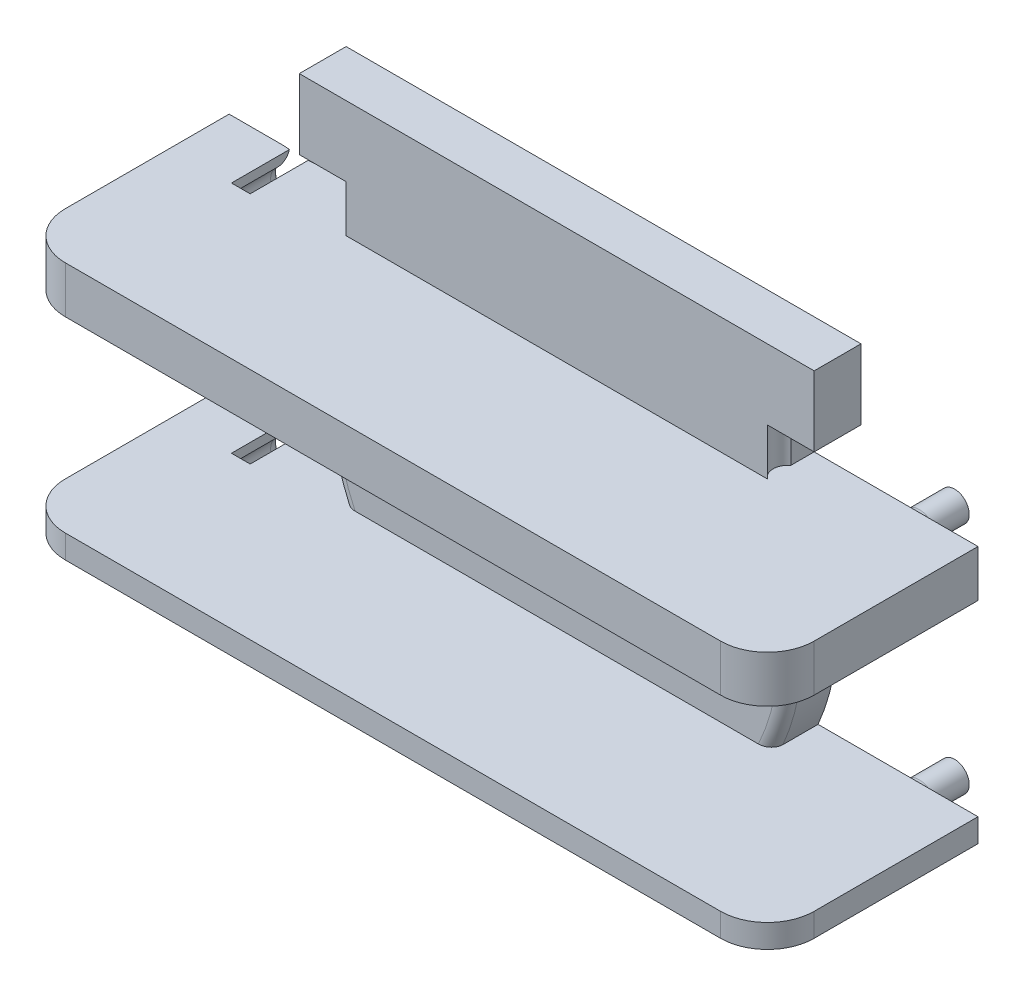
SolidWorks part; units mm, degrees
material "UNOBTANIUM"
ref_plane "Top Plane" through (0, 0, 0) normal (0, 0, 1) x (1, 0, 0)
ref_plane "Right Plane" through (0, 0, 0) normal (0, 1, 0) x (1, 0, 0)
ref_plane "Front Plane" through (0, 0, 0) normal (1, 0, 0) x (0, 0, -1)
ref_axis "x-axis" through (-17.6, 0, 0) along (1, 0, 0)
ref_axis "y-axis" through (0, -9.7375, 0) along (0, 1, 0)
ref_axis "z-axis" through (0, 0, 8.775) along (0, 0, -1)
sketch "Sketch1" plane through (0, 0, 0) normal (0, 0, 1) x (1, 0, 0)
  line L0 (-11, 6) -> (-11, 11)
  line L1 (-11, -6) -> (11, -6)
  line L2 (-11, -6) -> (-11, 6)
  line L3 (-11, 6) -> (11, 6) construction
  line L4 (11, -6) -> (11, 6)
  line L5 (-11, -6) -> (11, 6) construction
  line L6 (-11, 6) -> (11, -6) construction
  line L7 (-11, 11) -> (11, 11)
  line L8 (11, 11) -> (11, 6)
  circle A0 centre (0, 0) radius 9.25 construction
  point P0 (0, 0)
  dimension "D1" = 18.5
  dimension "D2" = 22
  dimension "D3" = 12
  dimension "D4" = 5
extrude "Boss-Extrude1" add sketch "Sketch1" along normal blind 2
sketch "Sketch2" plane through (0, 0, 2) normal (0, 0, -1) x (-1, 0, 0)
  circle A0 centre (0, 0) radius 1.575
  dimension "D1" = 3.15
extrude "Boss-Extrude2" add sketch "Sketch2" along normal blind 4 separate body
sketch "Sketch3" plane through (0, 0, 0) normal (0, 0, -1) x (-1, 0, 0)
  line L0 (11, -6) -> (-11, 6) construction
  circle A0 centre (0, 0) radius 1.8
  dimension "D1" = 3.6
extrude "Boss-Extrude3" add sketch "Sketch3" along normal blind 0.75
sketch "Sketch4" plane through (0, 0, 0) normal (0, 0, -1) x (-1, 0, 0)
  line L0 (11, -6) -> (-11, -6) construction
  line L1 (11, 11) -> (9, 11)
  line L2 (11, 11) -> (11, -6)
  line L3 (11, -6) -> (9, -6)
  line L4 (9, 11) -> (9, -6)
  line L5 (0, -6) -> (0, 11) construction
  line L7 (-9, 11) -> (-9, -6)
  line L8 (-11, -6) -> (-9, -6)
  line L9 (-11, 11) -> (-11, -6)
  line L10 (-11, 11) -> (-9, 11)
  line L11 (11, 11) -> (-11, 11) construction
  dimension "D1" = 2
extrude "Boss-Extrude4" add sketch "Sketch4" along normal blind 0.001
sketch "Sketch5" plane through (0, 0, 0) normal (0, 0, -1) x (-1, 0, 0)
  line L0 (-9, -6) -> (-9, 11) construction
  line L1 (9, 11) -> (-9, 11)
  line L2 (9, 11) -> (9, 9)
  line L3 (9, 9) -> (-9, 9)
  line L4 (-9, 11) -> (-9, 9)
  dimension "D1" = 2
extrude "Boss-Extrude5" add sketch "Sketch5" along normal up to surface (0.001 mm away) up to face at (-10, 2.5, -0.001)
sketch "Sketch6" plane through (11, 0, 0) normal (1, 0, 0) x (0, 0, -1)
  line L0 (-2, -6) -> (-2, 11) construction
  line L1 (0.001, -6) -> (-2, -6)
  line L2 (0.001, -6) -> (0.001, -4)
  line L3 (0.001, -4) -> (-2, -4)
  line L4 (-2, -6) -> (-2, -4)
  line L6 (0.001, 11) -> (0.001, -6) construction
  line L7 (-2, 6) -> (0.001, 6)
  line L8 (-2, 6) -> (-2, 4)
  line L9 (-2, 4) -> (0.001, 4)
  line L10 (0.001, 6) -> (0.001, 4)
  dimension "D1" = 2
extrude "Boss-Extrude6" add sketch "Sketch6" along normal blind 5
mirror "Mirror1" about plane through (0, 0, 0) normal (1, 0, 0) of "Boss-Extrude6"
sketch "Sketch7" plane through (0, 0, -0.001) normal (0, 0, -1) x (-1, 0, 0)
  line L0 (-9, -6) -> (-9, 9) construction
  line L1 (-9, 0) -> (-9, 9)
  line L2 (-9, 9) -> (0, 9)
  line L3 (-9, 0) -> (-9, -6)
  line L4 (-9, -6) -> (-6.7082, -6)
  line L5 (11, -6) -> (-11, -6) construction
  arc A0 (0, 9) -> (-6.7082, -6) centre (0, 0) ccw
  line M18 (-9, -6) -> (-9, 9)
  line M19 (-9, 9) -> (9, 9)
extrude "Boss-Extrude7" add sketch "Sketch7" against normal up to surface (0.001 mm away) contours A0 L4 M18 | A0 M19 M18 region at (8.3306, -4.5409, -0.001) region at (6.9897, 6.9897, -0.001) up to face at (1.8, 0, 0)
sketch "Sketch8" plane through (0, 0, -0.001) normal (0, 0, -1) x (-1, 0, 0)
  line L0 (-11, 4) -> (-9.1652, 4)
  line L1 (-11, 4) -> (-11, -4)
  line L2 (-11, -4) -> (-9.1652, -4)
  arc A1 (-9.1652, 4) -> (-9.1652, -4) centre (0, 0) ccw
  dimension "D1" = 10
extrude "Cut-Extrude1" cut sketch "Sketch8" against normal through all
sketch "Sketch9" plane through (0, 0, -0.001) normal (0, 0, -1) x (-1, 0, 0)
  line L0 (-16, -4) -> (-9.1652, -4) construction
  line L1 (-8.0623, 4) -> (-11, 4)
  line L2 (-8.0623, 4) -> (-8.0623, -4)
  line L3 (-8.0623, -4) -> (-11, -4)
  line L4 (-11, 4) -> (-11, -4)
  line L5 (-11, -6) -> (-11, 6) construction
  arc A0 (0, 9) -> (-6.7082, -6) centre (0, 0) ccw construction
  arc A1 (0, 9) -> (-6.7082, -6) centre (0, 0) ccw construction
extrude "Cut-Extrude2" cut sketch "Sketch9" against normal up to surface (0.001 mm away) up to face at (1.8, 0, 0)
mirror "Mirror2" about plane through (0, 0, 0) normal (1, 0, 0) of "Cut-Extrude2", "Boss-Extrude7", "Cut-Extrude1"
sketch "Sketch21" plane through (0, 0, -0.001) normal (0, 0, -1) x (-1, 0, 0)
  circle A0 centre (0, 0) radius 9.75
  circle A1 centre (0, 0) radius 9 construction
  circle A2 centre (0, 0) radius 1.8 construction
  circle A3 centre (0, 0) radius 1.8
  dimension "D1" = 0.75
extrude "Cut-Extrude11" cut sketch "Sketch21" against normal up to surface (0.001 mm away) up to face at (0, -0.7091, 0)
sketch "Sketch10" plane through (0, 0, 2) normal (0, 0, 1) x (1, 0, 0)
  line L0 (-16, -4) -> (-16, -6) construction
  line L1 (16, -6) -> (-16, -6)
  line L2 (16, -6) -> (16, -4)
  line L3 (16, -4) -> (-16, -4)
  line L4 (-16, -6) -> (-16, -4)
  line L5 (-16, -4) -> (-9.1652, -4) construction
  line L7 (-16, 6) -> (16, 6)
  line L8 (-16, 6) -> (-16, 4)
  line L9 (-16, 4) -> (16, 4)
  line L10 (16, 6) -> (16, 4)
extrude "Boss-Extrude8" add sketch "Sketch10" along normal blind 7
fillet "Fillet1" radius 0.5 2 edges at (10, 0, 2) (-10, 0, 2)
sketch "Sketch11" plane through (0, 0, -0.001) normal (0, 0, -1) x (-1, 0, 0)
  line L0 (-16, -5) -> (-13, -5) construction
  line L1 (-16, -6) -> (-16, -4) construction
  circle A0 centre (-13, -5) radius 0.625
  dimension "D1" = 1.25
  dimension "D2" = 3
extrude "Boss-Extrude9" add sketch "Sketch11" along normal blind 2
sketch "Sketch14" plane through (0, 0, -0.001) normal (0, 0, -1) x (-1, 0, 0)
  line L1 (11, 6) -> (9, 6)
  line L2 (11, 6) -> (11, 8)
  line L3 (11, 8) -> (9, 8)
  line L4 (9, 6) -> (9, 8)
  line L5 (-11, 6) -> (-9, 6)
  line L6 (-11, 6) -> (-11, 8)
  line L7 (-11, 8) -> (-9, 8)
  line L8 (-9, 6) -> (-9, 8)
  dimension "D1" = 18
  dimension "D2" = 2
extrude "Cut-Extrude5" cut sketch "Sketch14" against normal through all
sketch "Sketch12" plane through (0, 0, -0.001) normal (0, 0, -1) x (-1, 0, 0)
  line L0 (-16, -5) -> (-13, -5) construction
  line L1 (-16, -6) -> (-16, -4) construction
  line L3 (16, -5) -> (13, -5) construction
  line L4 (16, -6) -> (16, -4) construction
  circle A0 centre (13, -5) radius 0.725
  circle A1 centre (-13, -5) radius 0.625 construction
  circle A2 centre (-13, -5) radius 0.625 construction
  dimension "D1" = 1.45
  dimension "D2" = 1.25
extrude "Cut-Extrude3" cut sketch "Sketch12" against normal blind 2.5
sketch "Sketch16" plane through (0, 6, 0) normal (0, 1, 0) x (1, 0, 0)
  line L0 (-9, -2) -> (-9, 0.001) construction
  line L1 (-9, -1) -> (-9, -2)
  arc A1 (-9, -1) -> (-9, -2) centre (-9.375, -1.5) cw
  dimension "D1" = 0.25
  dimension "D2" = 1
extrude "Cut-Extrude6" cut sketch "Sketch16" along normal blind 2
mirror "Mirror3" about plane through (0, 0, 0) normal (0, 1, 0) of "Boss-Extrude9", "Cut-Extrude3"
mirror "Mirror4" about plane through (0, 0, 0) normal (1, 0, 0) of "Cut-Extrude6"
fillet "Fillet2" radius 0.5 2 edges at (12.375, 5, -0.001) (13.625, -5, -0.001)
fillet "Fillet3" radius 0.5 2 edges at (-13.725, 5, -0.001) (-13.725, -5, -0.001)
fillet "Fillet4" radius 2 4 edges at (16, -5, 9) (16, 5, 9) (-16, -5, 9) (-16, 5, 9)
sketch "Sketch17" plane through (0, -6, 0) normal (0, -1, 0) x (1, 0, 0)
  line L0 (-16, 7) -> (-16, -0.001) construction
  line L1 (-14, 9) -> (14, 9) construction
  line L2 (16, 7) -> (16, -0.001) construction
  line L3 (-16, 7) -> (-16, -0.001)
  line L4 (-14, 9) -> (14, 9)
  line L5 (16, 7) -> (16, -0.001)
  line L6 (14.5, 7) -> (14.5, -0.001)
  line L8 (-14, 7.5) -> (14, 7.5)
  line L9 (-14.5, 7) -> (-14.5, -0.001)
  line L10 (14.5, -0.001) -> (16, -0.001)
  line L11 (-14.5, -0.001) -> (-16, -0.001)
  arc A0 (-14, 9) -> (-16, 7) centre (-14, 7) ccw construction
  arc A1 (16, 7) -> (14, 9) centre (14, 7) ccw construction
  arc A2 (-14, 9) -> (-16, 7) centre (-14, 7) ccw
  arc A3 (16, 7) -> (14, 9) centre (14, 7) ccw
  arc A4 (14.5, 7) -> (14, 7.5) centre (14, 7) ccw
  arc A5 (-14, 7.5) -> (-14.5, 7) centre (-14, 7) ccw
  dimension "D1" = 1.5
extrude "Cut-Extrude7" cut sketch "Sketch17" against normal blind 1 and the other way through all
sketch "Sketch19" plane through (0, 6, 0) normal (0, 1, 0) x (1, 0, 0)
  line L0 (9, -2) -> (-9, -2) construction
  line L1 (0, -2.625) -> (0, -2) construction
  line L2 (9, -2) -> (-9, -2) construction
  circle A0 centre (0, -2.625) radius 0.625
  circle A1 centre (0, -8.125) radius 0.625
  point P4 (0, -2)
  dimension "D1" = 1.25
  dimension "D2" = 5.5
extrude "Cut-Extrude9" [suppressed] cut sketch "Sketch19" against normal up to surface (2 mm away)
sketch "Sketch20" plane through (0, 0, -0.001) normal (0, 0, -1) x (-1, 0, 0)
  line L0 (-9, 8) -> (-11, 8) construction
  line L1 (-11, 11) -> (-9, 11)
  line L2 (-11, 11) -> (-11, 8)
  line L3 (-11, 8) -> (-9, 8)
  line L4 (-9, 11) -> (-9, 8)
  line L5 (11, 11) -> (-11, 11) construction
  line L6 (11, 8) -> (9, 8)
  line L7 (11, 8) -> (11, 11)
  line L8 (11, 11) -> (9, 11)
  line L9 (9, 8) -> (9, 11)
  dimension "D1" = 2
combine bodies "Combine2" operation type subtract main body 120 bodies to subtract 102
sketch "Sketch23" plane through (0, 0, -0.001) normal (0, 0, -1) x (-1, 0, 0)
  line L0 (13, -6) -> (13, -4) construction
  line L1 (12.2925, -6) -> (13.7075, -6) construction
  line L2 (13.7075, -4) -> (12.2925, -4) construction
  line L3 (12.6, -6) -> (12.6, -4)
  line L4 (13.4, -6) -> (13.4, -4)
  arc A0 (12.6, -6) -> (13.4, -6) centre (13, -6) ccw
  arc A1 (13.4, -4) -> (12.6, -4) centre (13, -4) ccw
  point P6 (13, -5)
  dimension "D1" = 0.8
extrude "Cut-Extrude12" cut sketch "Sketch23" against normal up to surface (2.5 mm away) up to face at (-13.725, -5, 2.499)
mirror "Mirror5" about plane through (0, 0, 0) normal (0, 1, 0) of "Cut-Extrude12"
equation "\"D1@Sketch12\"=\"D2@Sketch12\"+.2"
